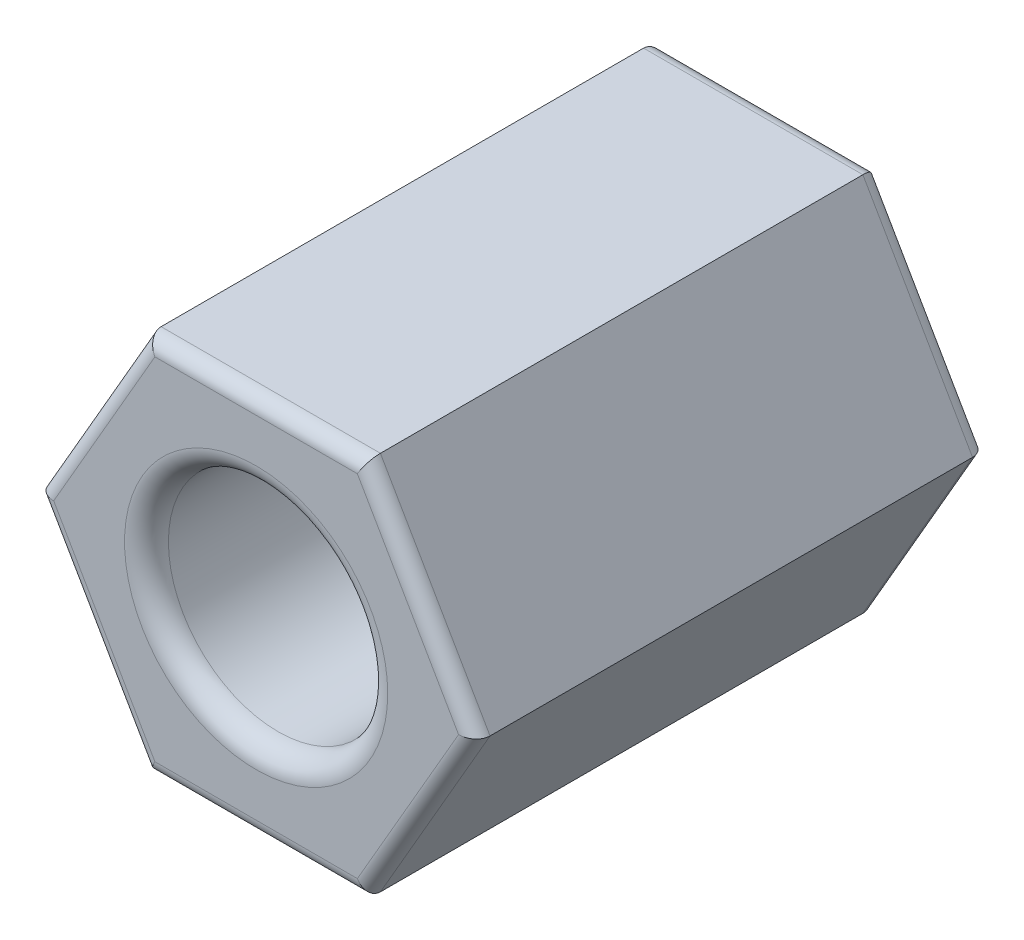
SolidWorks part; units mm, degrees
ref_plane "Front Plane" through (0, 0, 0) normal (0, 0, 1) x (1, 0, 0)
ref_plane "Top Plane" through (0, 0, 0) normal (0, 1, 0) x (1, 0, 0)
ref_plane "Right Plane" through (0, 0, 0) normal (1, 0, 0) x (0, 0, -1)
ref_axis "Axis1" through (0, 0, -10.0506) along (0, 0, 1)
sketch "Sketch1" plane through (0, 0, 0) normal (0, 0, 1) x (1, 0, 0)
  line L1 (3, 0) -> (1.5, 2.5981)
  line L2 (1.5, 2.5981) -> (-1.5, 2.5981)
  line L3 (-1.5, 2.5981) -> (-3, 0)
  line L4 (-3, 0) -> (-1.5, -2.5981)
  line L5 (-1.5, -2.5981) -> (1.5, -2.5981)
  line L6 (1.5, -2.5981) -> (3, 0)
  circle A0 centre (0, 0) radius 2.5981 construction
  circle A1 centre (0, 0) radius 1.5
  dimension "D2" = 3
  dimension "D1" = 6
extrude "Boss-Extrude1" add sketch "Sketch1" along normal blind 7
fillet "Fillet1" radius 0.3 2 edges at (1.5, 0, 0) (1.5, 0, 7)
fillet "Fillet2" radius 0.2 12 edges at (-2.25, 1.299, 7) (-2.25, -1.299, 7) (0, -2.5981, 7) (2.25, -1.299, 7) (2.25, 1.299, 7) (0, 2.5981, 7) (2.25, -1.299, 0) (0, -2.5981, 0) (-2.25, -1.299, 0) (-2.25, 1.299, 0) (0, 2.5981, 0) (2.25, 1.299, 0)
sketch "Sketch2" plane through (0, 0, 0) normal (0, 0, 1) x (1, 0, 0)
  circle A0 centre (0, 0) radius 3 construction
